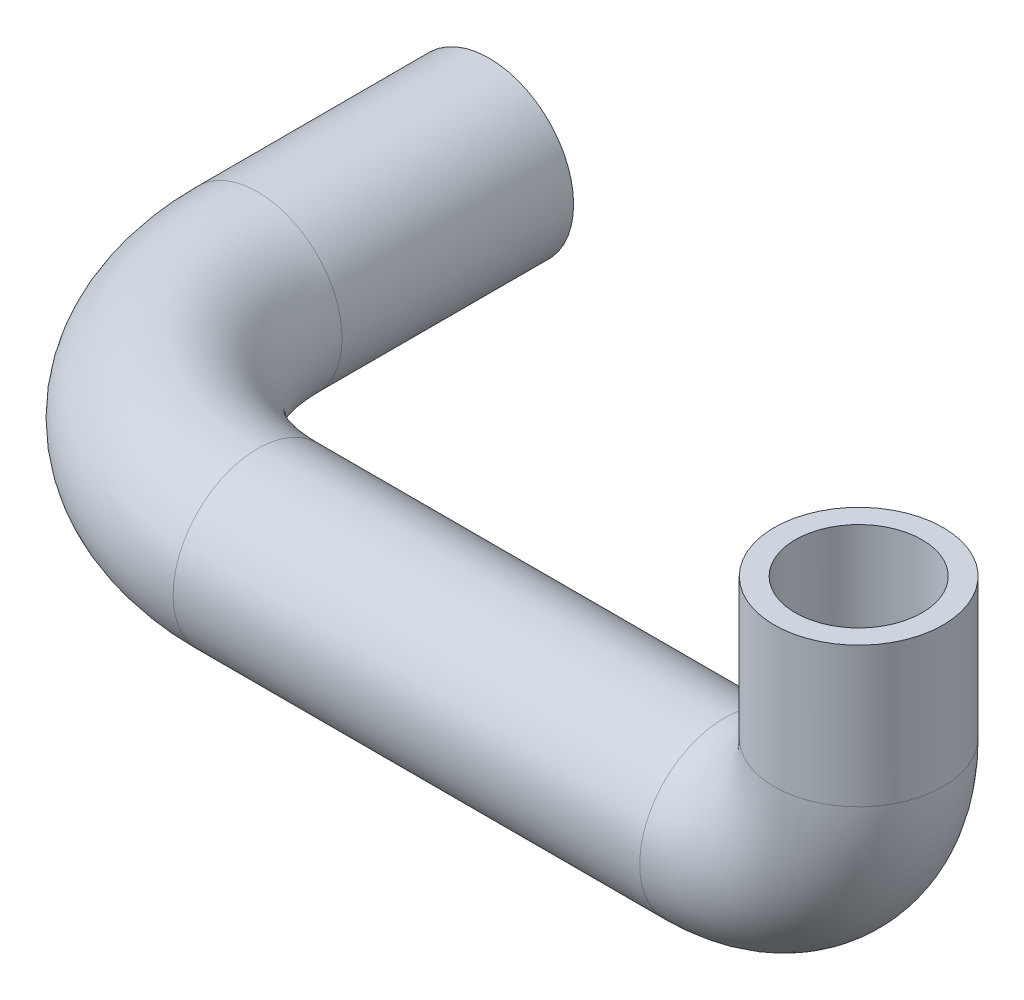
SolidWorks part; units mm, degrees
ref_plane "Front Plane" through (0, 0, 0) normal (0, 0, 1) x (1, 0, 0)
ref_plane "Top Plane" through (0, 0, 0) normal (0, 1, 0) x (1, 0, 0)
ref_plane "Right Plane" through (0, 0, 0) normal (1, 0, 0) x (0, 0, -1)
sketch "Sketch1" plane through (0, 0, 0) normal (0, 0, 1) x (1, 0, 0)
  circle A0 centre (0, 0) radius 8
  circle A1 centre (0, 0) radius 6
sketch3d "3DSketch1"
  line L0 (0, 0, 0) -> (0, 0, 21.93)
  line L1 (21.07, 0, 43) -> (65.26, 0, 43)
  line L2 (78, 12.74, 43) -> (78, 26, 43)
  arc A0 (0, 0, 21.93) -> (21.07, 0, 43) centre (21.07, 0, 21.93) cw
  arc A1 (65.26, 0, 43) -> (78, 12.74, 43) centre (65.26, 12.74, 43) cw
  point P4 (21.07, 21.07, 21.93)
  point P11 (65.26, 12.74, 55.74)
sweep "Sweep1" add path "3DSketch1" circular profile diameter 16 parameters "D3"=16
sweep "Hollow_tube_OD_and_wall_PROVISIONAL" cut path "3DSketch1<2>" circular profile diameter 12 parameters "D3"=12
sketch3d "3DSketch1<2>" same geometry as "3DSketch1"
